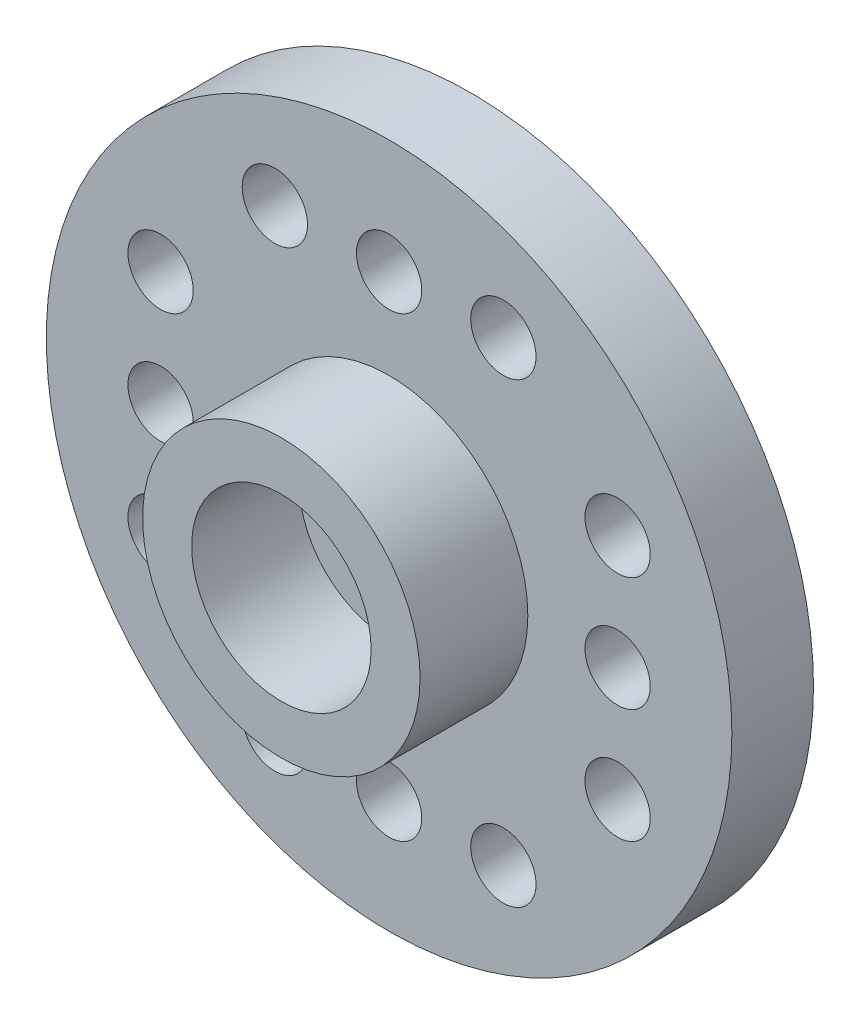
SolidWorks part; units mm, degrees
ref_plane "Front Plane" through (0, 0, 0) normal (0, 0, 1) x (1, 0, 0)
ref_plane "Top Plane" through (0, 0, 0) normal (0, 1, 0) x (1, 0, 0)
ref_plane "Right Plane" through (0, 0, 0) normal (1, 0, 0) x (0, 0, -1)
sketch "Sketch1" plane through (0, 0, 0) normal (0, 0, 1) x (1, 0, 0)
  circle A0 centre (0, 0) radius 10.5
  dimension "D1" = 21
extrude "Boss-Extrude1" add sketch "Sketch1" along normal blind 2.5 contours A0
sketch "Sketch2" plane through (0, 0, 2.5) normal (0, 0, 1) x (1, 0, 0)
  circle A0 centre (0, 0) radius 2.75
  circle A1 centre (0, 0) radius 4.25
  dimension "D1" = 5.5
  dimension "D2" = 8.5
extrude "Boss-Extrude2" add sketch "Sketch2" along normal blind 3.3
sketch "Sketch3" plane through (0, 0, 0) normal (0, 0, -1) x (-1, 0, 0)
  circle A0 centre (0, 0) radius 1.5
  circle A1 centre (0, 0) radius 4.7
  dimension "D1" = 3
extrude "Cut-Extrude1" cut sketch "Sketch3" against normal through all contours A0
extrude "Cut-Extrude2" cut sketch "Sketch3<3>" against normal blind 1.2 contours A1 A0 region at (4.5671, 0, 0)
sketch "Sketch3<3>" plane through (0, 0, 0) normal (0, 0, -1) x (-1, 0, 0) same geometry as "Sketch3"
sketch "Sketch4" plane through (0, 0, 1.2) normal (0, 0, -1) x (-1, 0, 0)
  circle A0 centre (0, 0) radius 3
  circle A1 centre (0, 0) radius 3.15
extrude "Boss-Extrude3" add sketch "Sketch4" along normal blind 1.2
sketch "Sketch5" plane through (0, 0, 0) normal (0, 0, -1) x (-1, 0, 0)
  line L0 (-999.2317, 7) -> (49000.7683, 7) construction
  line L1 (-1000, -7) -> (-1000, 49993) construction
  line L2 (-7, -1000.6111) -> (-7, 48999.3889) construction
  line L3 (7, -999.7506) -> (7, 49000.2494) construction
  line L4 (-1000, -7) -> (49000, -7) construction
  circle A0 centre (0, 0) radius 7 construction
  circle A1 centre (0, 7) radius 1
  circle A2 centre (0, -7) radius 1
  circle A3 centre (-7, 0) radius 1
  circle A4 centre (7, 0) radius 1
  circle A5 centre (3.5, 7) radius 1
  circle A6 centre (-3.5, 7) radius 1
  circle A7 centre (-7, 3.5) radius 1
  circle A8 centre (-7, -3.5) radius 1
  circle A9 centre (7, -3.5) radius 1
  circle A10 centre (7, 3.5) radius 1
  circle A11 centre (-3.5, -7) radius 1
  circle A12 centre (3.5, -7) radius 1
  dimension "D1" = 3.5
  dimension "D2" = 3.5
  dimension "D3" = 3.5
  dimension "D7" = 3.5
  dimension "D9" = 2
  dimension "D10" = 2
  dimension "D11" = 2
  dimension "D12" = 14
  dimension "D4" = 3.5
  dimension "D5" = 3.5
  dimension "D6" = 3.5
  dimension "D8" = 3.5
extrude "Cut-Extrude3" cut sketch "Sketch5" against normal through all
